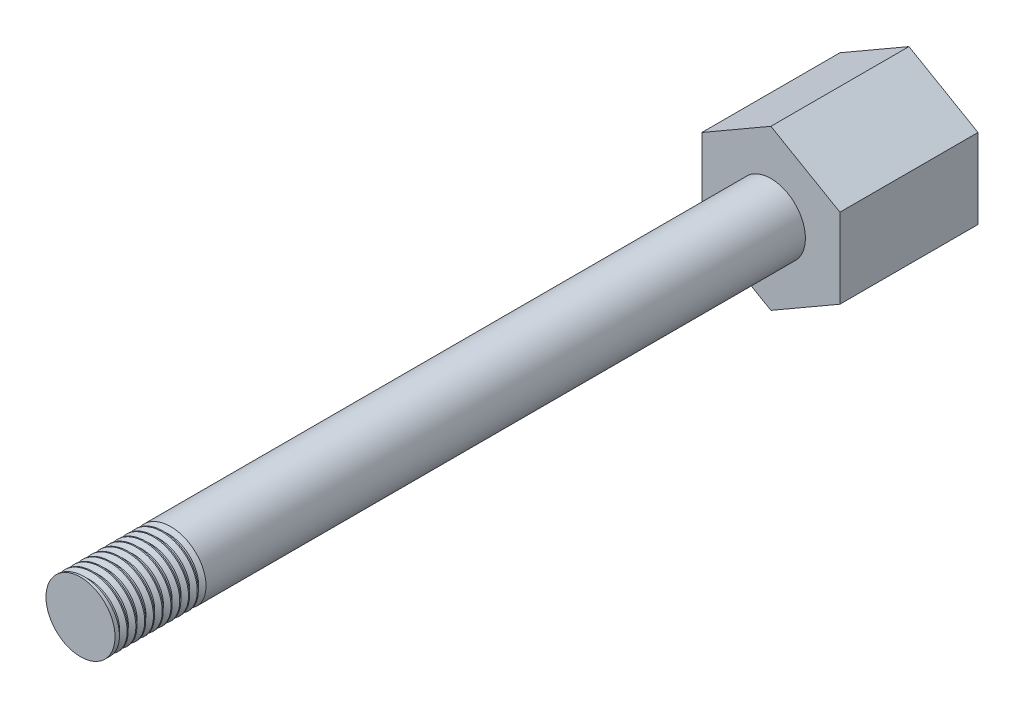
SolidWorks part; units mm, degrees
ref_plane "Front Plane" through (0, 0, 0) normal (0, 0, 1) x (1, 0, 0)
ref_plane "Top Plane" through (0, 0, 0) normal (0, 1, 0) x (1, 0, 0)
ref_plane "Right Plane" through (0, 0, 0) normal (1, 0, 0) x (0, 0, -1)
sketch "Sketch1" plane through (0, 0, 0) normal (0, 0, 1) x (1, 0, 0)
  line L1 (0, -5.7735) -> (5, -2.8868)
  line L2 (5, -2.8868) -> (5, 2.8868)
  line L3 (5, 2.8868) -> (0, 5.7735)
  line L4 (0, 5.7735) -> (-5, 2.8868)
  line L5 (-5, 2.8868) -> (-5, -2.8868)
  line L6 (-5, -2.8868) -> (0, -5.7735)
  circle A1 centre (0, 0) radius 5 construction
extrude "Boss-Extrude1" add sketch "Sketch1" along normal blind 10
sketch "Sketch2" plane through (0, 0, 10) normal (0, 0, 1) x (1, 0, 0)
  circle A0 centre (0, 0) radius 2.5
extrude "Boss-Extrude2" add sketch "Sketch2" along normal blind 50
thread "Thread1" pitch 0.635 method cut profile "Thread Profile1" start angle 0, offset 0, length 0, pitch 0.635, diameter 5
ref_plane "Plane1" through (-2.5, 0, 60) normal (0, -1, 0) x (-1, 0, 0)
sketch "Thread Profile1" plane through (-2.5, 0, 60) normal (0, -1, 0) x (-1, 0, 0)
  line L0 (0, 0) -> (0, 0.635) construction
  line L11 (0, 0) -> (0, 0.5556)
  line L12 (0, 0.5556) -> (-0.3437, 0.3572)
  line L13 (-0.3437, 0.3572) -> (-0.3437, 0.1984)
  line L15 (-0.3437, 0.1984) -> (0, 0)
  line L17 (-0.3437, 0.2778) -> (0, 0.2778) construction
  point P2 (0, 0)
  dimension "Pitch" = 0.635
  dimension "Profile_Angle" = 60
  dimension "Profile_Land" = 0.1588
  dimension "Profile_Height" = 0.3437
